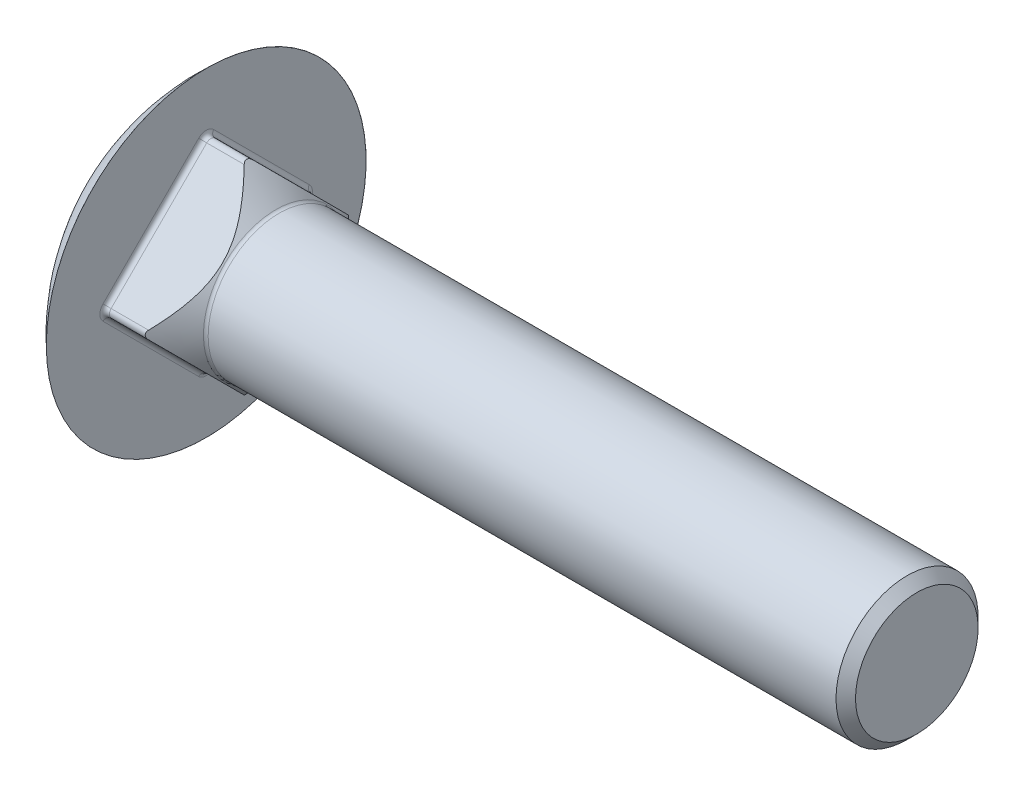
SolidWorks part; units mm, degrees
ref_plane "Front" through (0, 0, 0) normal (0, 0, 1) x (1, 0, 0)
ref_plane "Top" through (0, 0, 0) normal (0, 1, 0) x (1, 0, 0)
ref_plane "Right" through (0, 0, 0) normal (1, 0, 0) x (0, 0, -1)
sketch "Sketch1" plane through (0, 0, 0) normal (0, 0, 1) x (1, 0, 0)
  line L0 (-9.8282, 0) -> (16.3483, 0) construction
  line L1 (11.9999, 27) -> (12, 27)
  line L2 (0, 0) -> (12, 0)
  line L3 (12, 27) -> (12, 0)
  arc A0 (11.9999, 27) -> (0, 0) centre (36.3752, 0) ccw
  dimension "Head_dia" = 54
  dimension "Head_thickness" = 12
  dimension "H" = 0.0001
revolve "BaseHead" add sketch "Sketch1" angle 360 about L0
sketch "Sketch2" plane through (12, 0, 0) normal (1, 0, 0) x (0, 0, -1)
  line L1 (-17.5645, 0) -> (0, -17.5645)
  line L2 (0, -17.5645) -> (17.5645, 0)
  line L3 (17.5645, 0) -> (0, 17.5645)
  line L4 (0, 17.5645) -> (-17.5645, 0)
  circle A0 centre (0, 0) radius 12.42 construction
  dimension "square_neck" = 24.84
extrude "Neck" add sketch "Sketch2" along normal blind 12
sketch "Sketch3" plane through (0, 0, 0) normal (0, 0, 1) x (1, 0, 0)
  line L0 (5, 0) -> (14.6279, 0) construction
  line L1 (24, 17.5645) -> (18.4355, 17.5645)
  line L3 (18.4355, 17.5645) -> (24, 12)
  line L5 (24, 12) -> (24, 17.5645)
  dimension "D1" = 45
  dimension "D2" = 24
revolve "Cut-Revolve1" cut sketch "Sketch3" angle 360 about L0
fillet "RaCornNeck" radius 1 4 edges at (15.2177, 17.5645, 0) (15.2177, 0, 17.5645) (15.2177, -17.5645, 0) (15.2177, 0, -17.5645)
fillet "HeadFillet" radius 0.8 8 edges at (12, 8.7823, -8.7823) (12, -8.7823, -8.7823) (12, -8.7823, 8.7823) (12, 8.7823, 8.7823) (12, 17.1503, 0) (12, 0, -17.1503) (12, -17.1503, 0) (12, 0, 17.1503)
sketch "BodySke" plane through (0, 0, 0) normal (0, 1, 0) x (1, 0, 0)
  line L0 (-12.2854, 0) -> (141.5775, 0) construction
  line L1 (130.352, 12) -> (24, 12)
  line L2 (78, 18.4981) -> (78, -12.5734) construction
  line L4 (12, -27) -> (12, 27) construction
  line L5 (132, 10.352) -> (132, 0)
  line L6 (132, 0) -> (24, 0)
  line L7 (24, 0) -> (24, 12)
  line L8 (129, 21.1398) -> (129, -17.9826) construction
  line L9 (130.352, 12) -> (132, 10.352)
  line L10 (24, -12) -> (24, 12) construction
revolve "BaseBody" add sketch "BodySke" angle 360 about L0
cosmetic thread "ThreadCosmetic" [suppressed] parameters "D1"=54, "dn"=20.704
fillet "NeckFillet" radius 0.8 1 edges at (24, 0, 12)
sketch "ThdSchSke" plane through (0, 0, 0) normal (0, 0, 1) x (1, 0, 0)
  line L0 (128.0485, 13.9029) -> (129.9515, 13.9029)
  line L1 (129.9515, 13.9029) -> (129.9515, 12)
  line L2 (129.9515, 12) -> (129, 10.352)
  line L3 (128.0485, 12) -> (129, 10.352)
  line L4 (128.0485, 13.9029) -> (128.0485, 12)
  line L5 (-65.6461, 0) -> (65.6461, 0) construction
  line L6 (128.0485, 12) -> (129.9515, 12) construction
  line L7 (129, 12) -> (129, 10.352) construction
  line L10 (132, -10.352) -> (132, 10.352) construction
  dimension "D3" = 3
  dimension "D4" = 24
  dimension "D1" = 20.704
revolve "ThreadSchematic" [suppressed] cut sketch "ThdSchSke" angle 360 about L5
pattern_linear "ThdSchPat" [suppressed] count 17 spacing 3 along (-1, 0, 0) of bodies 106
equation "\"D3@ThdSchPat\" =\"Advance@BodySke\""
equation "\"D1@ThdSchPat\" =  int( \"Thread_length@BodySke\"/\"Advance@BodySke\") -1"
equation "\"D1@NeckFillet\"=\"r_headandneck@HeadFillet\""
equation "\"D1@ThdSchSke\"=\"Minor_dia@BodySke\""
equation "\"D4@ThdSchSke\"=\"Diameter@BodySke\""
equation "\"D3@ThdSchSke\"=\"Advance@BodySke\""
equation "\"D2@Sketch3\"=\"Diameter@BodySke\""
equation "\"D1@ThreadCosmetic\"=\"Thread_length@BodySke\""
equation "\"dn@ThreadCosmetic\" = \"Minor_dia@BodySke\""
